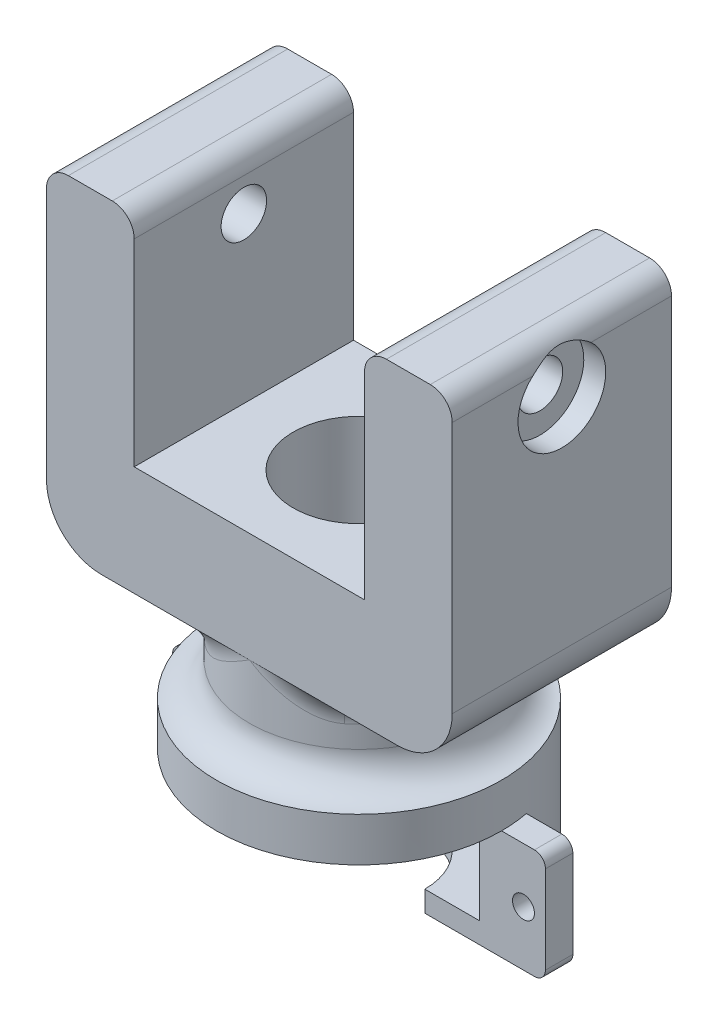
SolidWorks part; units mm, degrees
note: The reader was unsure of these and kept them because the rebuilt part matched: shared geometry of "Sketch16<2>".
material "Polylactide (PLA)"
ref_plane "Front Plane" through (0, 0, 0) normal (0, 0, 1) x (1, 0, 0)
ref_plane "Top Plane" through (0, 0, 0) normal (0, 1, 0) x (1, 0, 0)
ref_plane "Right Plane" through (0, 0, 0) normal (1, 0, 0) x (0, 0, -1)
sketch "Sketch1" plane through (0, 0, 0) normal (0, 0, 1) x (1, 0, 0)
  line L0 (0, 0) -> (0, 30)
  line L1 (0, 30) -> (8, 30)
  line L2 (8, 30) -> (8, 10)
  line L3 (8, 10) -> (29, 10)
  line L4 (29, 10) -> (29, 30)
  line L5 (29, 30) -> (37, 30)
  line L6 (37, 30) -> (37, 0)
  line L7 (37, 0) -> (0, 0)
  dimension "D1" = 21
  dimension "D2" = 8
  dimension "D3" = 8
  dimension "D4" = 30
  dimension "D5" = 10
  dimension "D6" = 30
extrude "Boss-Extrude1" add sketch "Sketch1" along normal blind 20
sketch "Sketch2" plane through (37, 0, 0) normal (1, 0, 0) x (0, 0, -1)
  line L0 (-20, 0) -> (0, 0) construction
  circle A0 centre (-10, 25) radius 2.075
  point P4 (-10, 0)
  dimension "D2" = 4.15
  dimension "D1" = 25
extrude "Cut-Extrude1" cut sketch "Sketch2" against normal blind 50
sketch "Sketch3" plane through (0, 0, 0) normal (0, -1, 0) x (1, 0, 0)
  line L0 (0, 0) -> (37, 0) construction
  line L1 (0, 20) -> (0, 0) construction
  circle A0 centre (18.5, 10) radius 10
  point P4 (18.5, 0)
  point P7 (0, 10)
  dimension "D1" = 20
extrude "Boss-Extrude2" add sketch "Sketch3" along normal blind 10
fillet "Fillet3" radius 5 2 edges at (37, 0, 10) (0, 0, 10)
fillet "Fillet4" radius 2 4 edges at (0, 30, 10) (8, 30, 10) (29, 30, 10) (37, 30, 10)
sketch "Sketch4" plane through (0, -10, 0) normal (0, -1, 0) x (1, 0, 0)
  circle A1 centre (18.5, 10) radius 13
  dimension "D2" = 26
extrude "Boss-Extrude3" add sketch "Sketch4" along normal blind 10 separate body
sketch "Sketch5" plane through (0, -20, 0) normal (0, -1, 0) x (1, 0, 0)
  line L0 (18.5, 23) -> (18.5, -3) construction
  circle A0 centre (18.5, 10) radius 13 construction
  circle A1 centre (18.5, 10) radius 11
  dimension "D1" = 22
extrude "Cut-Extrude2" cut sketch "Sketch5" against normal blind 8
sketch "Sketch7" plane through (0, -10, 0) normal (0, 1, 0) x (1, 0, 0)
  line L0 (18.5, 3) -> (18.5, -23) construction
  circle A0 centre (18.5, -10) radius 13 construction
  circle A1 centre (18.5, -10) radius 13
extrude "Boss-Extrude4" add sketch "Sketch7" along normal blind 2
sketch "Sketch8" plane through (0, -12, 0) normal (0, -1, 0) x (1, 0, 0)
  circle A0 centre (18.5, 10) radius 3.1
  point P0 (18.5, 10)
  dimension "D1" = 6.2
extrude "Cut-Extrude3" cut sketch "Sketch8" against normal blind 10
sketch "Sketch9" plane through (0, -12, 0) normal (0, -1, 0) x (1, 0, 0)
  circle A0 centre (18.5, 10) radius 6
  dimension "D1" = 12
extrude "Cut-Extrude4" cut sketch "Sketch9" against normal blind 20 from offset 5 offset against normal yes
fillet "Fillet7" radius 3 1 edges at (8.5, -8, 10)
fillet "Fillet8" radius 3 2 edges at (8.5, 0, 10) (28.5, 0, 10)
sketch "Sketch10" plane through (37, 0, 0) normal (1, 0, 0) x (0, 0, -1)
  circle A0 centre (-10, 25) radius 4
  dimension "D1" = 8
extrude "Cut-Extrude5" cut sketch "Sketch10" against normal blind 2
sketch "Sketch11" plane through (0, 0, 0) normal (-1, 0, 0) x (0, 0, 1)
  circle A0 centre (10, 25) radius 4
  dimension "D1" = 8
extrude "Cut-Extrude6" cut sketch "Sketch11" against normal blind 2
sketch "Sketch12" plane through (0, -20, 0) normal (0, -1, 0) x (1, 0, 0)
  circle A0 centre (18.5, 10) radius 13
extrude "Boss-Extrude5" add sketch "Sketch12" along normal blind 2
sketch "Sketch13" plane through (0, -7, 0) normal (0, 1, 0) x (1, 0, 0)
  circle A0 centre (18.5, -10) radius 6
extrude "Cut-Extrude7" cut sketch "Sketch13" against normal blind 23
sketch "Sketch14" plane through (0, 0, 0) normal (1, 0, 0) x (0, 0, -1)
  line L0 (-23, -22) -> (3, -22) construction
  line L1 (-10, -22) -> (-28.1377, -22)
  line L2 (-10, -22) -> (-10, -12)
  line L3 (-10, -12) -> (-28.1377, -12)
  line L4 (-28.1377, -22) -> (-28.1377, -12)
  dimension "D1" = 10
extrude "Cut-Extrude8" cut sketch "Sketch14" along normal blind 36
sketch "Sketch15" plane through (0, -20, 0) normal (0, 1, 0) x (1, 0, 0)
  circle A0 centre (18.5, -10) radius 11
  dimension "D1" = 22
extrude "Cut-Extrude9" cut sketch "Sketch15" against normal blind 0.1
sketch "Sketch16" plane through (0, 0, 0) normal (1, 0, 0) x (0, 0, -1)
  line L1 (-10, -22) -> (-7.5, -22)
  line L2 (-10, -22) -> (-10, -12)
  line L3 (-10, -12) -> (-7.5, -12)
  line L4 (-7.5, -22) -> (-7.5, -12)
  dimension "D1" = 10
  dimension "D2" = 2.5
extrude "Boss-Extrude6" add sketch "Sketch16" along normal blind 5 from offset 1.5
extrude "Boss-Extrude7" add sketch "Sketch16<2>" along normal blind 5.5 from offset 30
sketch "Sketch16<2>" plane through (0, 0, 0) normal (1, 0, 0) x (0, 0, -1) same geometry as "Sketch16"
sketch "Sketch17" plane through (0, 0, 7.5) normal (0, 0, -1) x (-1, 0, 0)
  line L0 (-5.7426, -12) -> (-1.5, -12) construction
  line L1 (-1.5, -22) -> (-1.5, -12) construction
  circle A0 centre (-3.5, -17) radius 1
  dimension "D1" = 5
  dimension "D2" = 2
  dimension "D3" = 2
extrude "Cut-Extrude10" cut sketch "Sketch17" against normal blind 5.5
sketch "Sketch18" plane through (0, 0, 7.5) normal (0, 0, -1) x (-1, 0, 0)
  line L0 (-35.5, -12) -> (-31.2574, -12) construction
  line L1 (-35.5, -22) -> (-35.5, -12) construction
  circle A0 centre (-33.5, -17) radius 1
  dimension "D1" = 5
  dimension "D2" = 2
  dimension "D3" = 2
extrude "Cut-Extrude11" cut sketch "Sketch18" against normal blind 5.5
sketch "Sketch19" plane through (0, 0, 7.5) normal (0, 0, -1) x (-1, 0, 0)
  circle A0 centre (-33.5, -17) radius 3
  dimension "D1" = 6
extrude "Cut-Extrude12" cut sketch "Sketch19" along normal blind 10.5
sketch "Sketch20" plane through (0, 0, 7.5) normal (0, 0, -1) x (-1, 0, 0)
  circle A0 centre (-3.5, -17) radius 3
  dimension "D1" = 6
extrude "Cut-Extrude13" cut sketch "Sketch20" along normal blind 12.5
fillet "Fillet9" radius 1 1 edges at (35.5, -12, 8.75)
fillet "Fillet10" radius 1 1 edges at (35.5, -22, 8.75)
fillet "Fillet11" radius 1 1 edges at (1.5, -12, 8.75)
fillet "Fillet12" radius 1 1 edges at (1.5, -22, 8.75)
